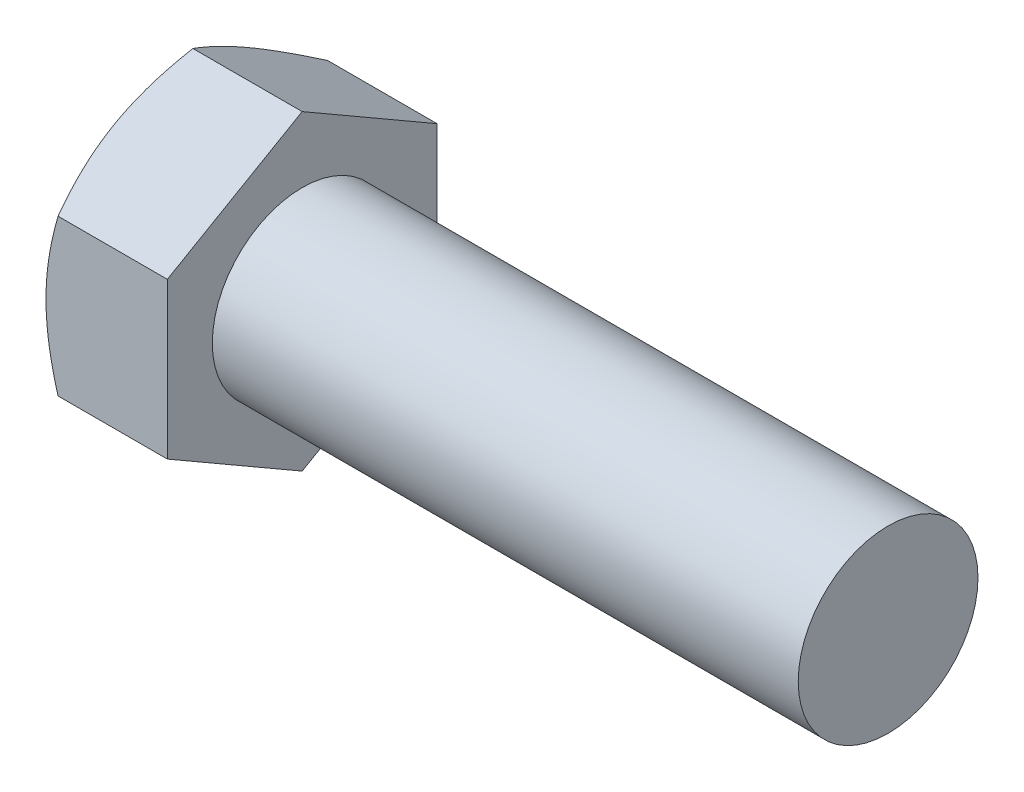
SolidWorks part; units mm, degrees
material "Plain Carbon Steel"
ref_plane "Front Plane" through (0, 0, 0) normal (0, 0, 1) x (1, 0, 0)
ref_plane "Top Plane" through (0, 0, 0) normal (0, 1, 0) x (1, 0, 0)
ref_plane "Right Plane" through (0, 0, 0) normal (1, 0, 0) x (0, 0, -1)
sketch "Sketch1" plane through (0, 0, 0) normal (0, 0, 1) x (1, 0, 0)
  line L0 (-30.7578, 0) -> (30.7578, 0) construction
  line L1 (30.7578, 7.9375) -> (30.7578, -7.9375) construction
  line L2 (-20.0422, 11.9062) -> (-20.0422, -11.9062) construction
  line L3 (-30.7578, 11.9062) -> (-30.7578, -11.9062) construction
  point P9 (-20.0422, 0)
  point P10 (22.676, -7.9375)
  dimension "Screw Dia" = 15.875
  dimension "Hex" = 23.8125
  dimension "Head Ht" = 10.7156
  dimension "Screw Lenght" = 50.8
  dimension "D1" = 8.0818
ref_plane "Plane2" through (30.7578, 0, 0) normal (1, 0, 0) x (0, 0, -1)
sketch "Sketch5" plane through (30.7578, 0, 0) normal (1, 0, 0) x (0, 0, -1)
  circle A0 centre (0, 0) radius 7.9375
extrude "Boss-Extrude3" add sketch "Sketch5" against normal up to vertex (50.8 mm away) up to point (-20.0422, 0, 0)
sketch "Sketch9" plane through (30.7578, 0, 0) normal (1, 0, 0) x (0, 0, -1)
  circle A1 centre (0, 0) radius 7.9375
  circle A2 centre (0, 0) radius 7.9375
  dimension "D1" = 0
curve "Helix/Spiral1" pitch 2.3091 height 53.1091 turns 23 parameters "Pitch"=2.3091
chamfer "Chamfer1" distance 1.7318 angle 45 1 edges at (30.7578, 0, -7.9375)
sketch "Sketch10" plane through (0, 0, 0) normal (0, 0, 1) x (1, 0, 0)
  line L0 (30.7578, 7.9375) -> (31.6237, 6.4377)
  line L1 (31.6237, 6.4377) -> (31.9124, 6.4377)
  line L2 (31.9124, 6.4377) -> (32.7783, 7.9375)
  line L3 (30.7578, 7.9375) -> (32.7783, 7.9375)
  line L4 (31.768, 7.9375) -> (31.768, 6.4377) construction
  line L5 (31.1908, 7.1876) -> (32.3453, 7.1876) construction
  dimension "D1" = 60
  dimension "D2" = 0.2886
  dimension "D3" = 1.1545
sweep "Cut-Sweep1" cut profiles "Sketch10" path "Helix/Spiral1"
sketch "Sketch6" plane through (-20.0422, 0, 0) normal (-1, 0, 0) x (0, 0, 1)
  line L0 (0, 11.9062) -> (0, -11.9062) construction
  line L1 (11.9062, 6.8741) -> (0, 13.7482)
  line L2 (0, 13.7482) -> (-11.9062, 6.8741)
  line L3 (-11.9062, 6.8741) -> (-11.9062, -6.8741)
  line L4 (-11.9062, -6.8741) -> (0, -13.7482)
  line L5 (0, -13.7482) -> (11.9063, -6.8741)
  line L6 (11.9063, -6.8741) -> (11.9062, 6.8741)
  circle A0 centre (0, 0) radius 11.9062 construction
extrude "Boss-Extrude4" add sketch "Sketch6" along normal up to vertex (10.7156 mm away) up to point (-30.7578, -11.9062, 0)
sketch "Sketch7" plane through (-30.7578, 0, 0) normal (-1, 0, 0) x (0, 0, 1)
  circle A0 centre (0, 0) radius 11.9062 construction
  circle A1 centre (0, 0) radius 11.9062
sketch "Sketch8" plane through (-30.7578, 0, 0) normal (-1, 0, 0) x (0, 0, 1)
  circle A0 centre (0, 0) radius 11.9062 construction
  circle A1 centre (0, 0) radius 11.9062
extrude "Cut-Extrude3" cut sketch "Sketch8" against normal through all draft 60 flip side to cut
sketch "Sketch12" plane through (-30.7578, 0, 0) normal (-1, 0, 0) x (0, 0, 1)
  line L0 (0, 9.1678) -> (0, 5.1197) construction
  line L1 (0.3572, 9.1678) -> (0.3572, 5.1197)
  line L2 (-0.3572, 9.1678) -> (-0.3572, 5.1197)
  line L3 (0, 7.9375) -> (0, -7.9375) construction
  arc A0 (0.3572, 9.1678) -> (-0.3572, 9.1678) centre (0, 9.1678) ccw
  arc A1 (-0.3572, 5.1197) -> (0.3572, 5.1197) centre (0, 5.1197) ccw
  circle A3 centre (0, 0) radius 4.7625 construction
  circle A4 centre (0, 0) radius 9.525 construction
  point P2 (0, 7.1438)
  dimension "D1" = 9.525
  dimension "D3" = 19.05
  dimension "D2" = 0.7144
extrude "Cut-Extrude4" cut sketch "Sketch12" against normal blind 0.254
pattern_circular "CirPattern1" count 6 over 360 about axis through (0, 0, 0) along (1, 0, 0) of "Cut-Extrude4"
sketch "Sketch13" plane through (-20.0422, 0, 0) normal (1, 0, 0) x (0, 0, -1)
  circle A0 centre (0, 0) radius 7.9375
  dimension "D1" = 15.875
extrude "Boss-Extrude5" add sketch "Sketch13" along normal through all
equation "\"D2@Sketch10\" = \"Pitch@Helix/Spiral1\"*.125"
equation "\"D3@Sketch10\" = \"Pitch@Helix/Spiral1\"*.5"
equation "\"D3@Helix/Spiral1\" = \"Screw Lenght@Sketch1\"+\"Pitch@Helix/Spiral1\""
equation "\"D1@Chamfer1\" = \"Pitch@Helix/Spiral1\"*.75"
equation "\"D1@Sketch12\" = \"Hex@Sketch1\"*.4"
equation "\"D3@Sketch12\" = \"Hex@Sketch1\"*.8"
equation "\"D2@Sketch12\" = \"Hex@Sketch1\"*.03"
equation "\"D1@Sketch1\" = \"Pitch@Helix/Spiral1\"*3.5"
